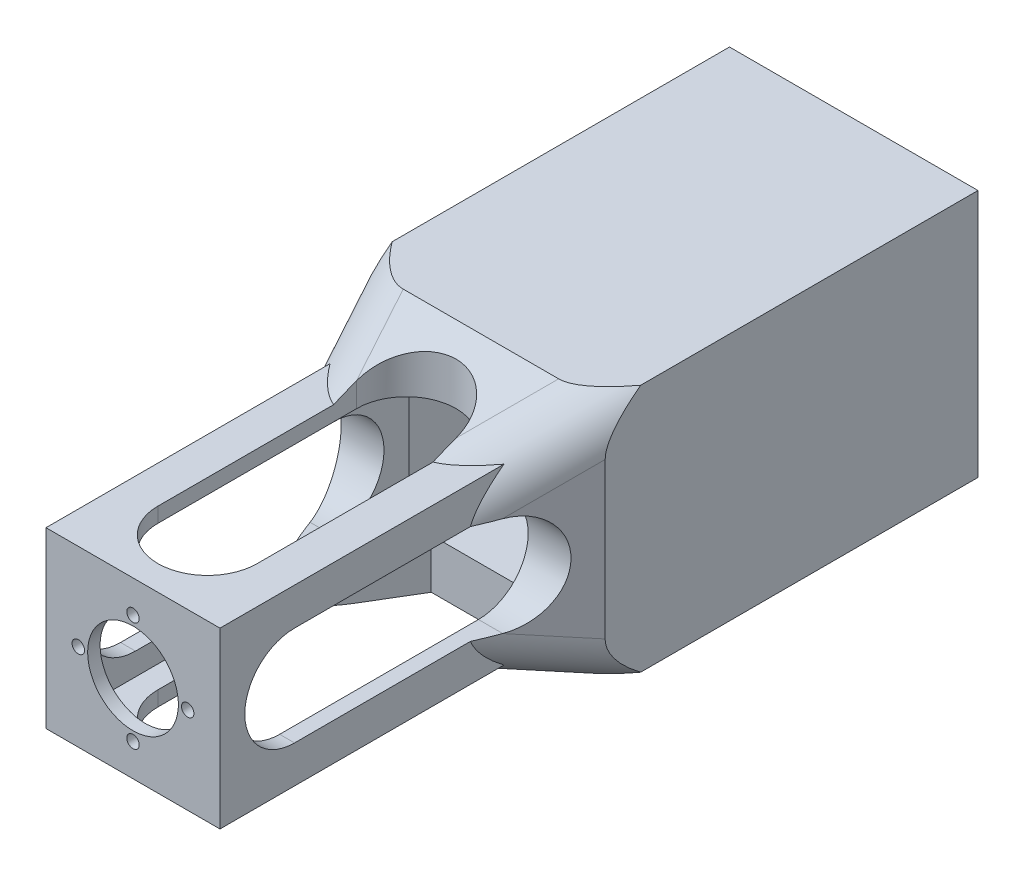
SolidWorks part; units mm, degrees
ref_plane "Ön Düzlem" through (0, 0, 0) normal (0, 0, 1) x (1, 0, 0)
ref_plane "Üst Düzlem" through (0, 0, 0) normal (0, 1, 0) x (1, 0, 0)
ref_plane "Sağ Düzlem" through (0, 0, 0) normal (1, 0, 0) x (0, 0, -1)
sketch "Çizim1" plane through (0, 0, 0) normal (0, 0, 1) x (1, 0, 0)
  line L0 (-14.5, 14.5) -> (14.5, 14.5)
  line L1 (-17.5, 17.5) -> (17.5, 17.5)
  line L2 (-17.5, 17.5) -> (-17.5, -17.5)
  line L3 (-17.5, -17.5) -> (17.5, -17.5)
  line L4 (17.5, 17.5) -> (17.5, -17.5)
  line L5 (-17.5, 17.5) -> (17.5, -17.5) construction
  line L6 (-17.5, -17.5) -> (17.5, 17.5) construction
  line L7 (14.5, 14.5) -> (14.5, -14.5)
  line L8 (-14.5, -14.5) -> (14.5, -14.5)
  line L9 (-14.5, 14.5) -> (-14.5, -14.5)
  point P0 (0, 0)
  dimension "D1" = 35
  dimension "D2" = 3
extrude "Yükseklik-Ekstrüzyon1" add sketch "Çizim1" along normal mid plane 70
sketch "Çizim2" plane through (0, 0, 35) normal (0, 0, 1) x (1, 0, 0)
  line L1 (-17.5, -17.5) -> (17.5, -17.5)
  line L2 (-17.5, -17.5) -> (-17.5, 17.5)
  line L3 (-17.5, 17.5) -> (17.5, 17.5)
  line L4 (17.5, -17.5) -> (17.5, 17.5)
  line L5 (-17.5, -17.5) -> (17.5, 17.5) construction
  line L6 (-17.5, 17.5) -> (17.5, -17.5) construction
  point P0 (0, 0)
extrude "Yükseklik-Ekstrüzyon2" add sketch "Çizim2" against normal blind 2.5
ref_axis "Eksen1" through (0, 0, -55) along (0, 0, 1)
sketch "Çizim7" plane through (0, 0, 35) normal (0, 0, 1) x (1, 0, 0)
  circle A0 centre (-11, 0) radius 1.25
  circle A1 centre (11, 0) radius 1.25
  circle A2 centre (0, 11) radius 1.25
  circle A3 centre (0, -11) radius 1.25
extrude "Kes-Ekstrüzyon5" cut sketch "Çizim7" against normal through all
sketch "Çizim5" plane through (0, 0, 32.5) normal (0, 0, -1) x (-1, 0, 0)
  circle A0 centre (0, 0) radius 9.125
  dimension "D1" = 18.25
extrude "Kes-Ekstrüzyon3" cut sketch "Çizim5" against normal through all contours A0
sketch "Çizim10" plane through (0, 0, -35) normal (0, 0, -1) x (-1, 0, 0)
  line L1 (-25, 25) -> (25, 25)
  line L2 (-25, 25) -> (-25, -25)
  line L3 (-25, -25) -> (25, -25)
  line L4 (25, 25) -> (25, -25)
  line L5 (-25, 25) -> (25, -25) construction
  line L6 (-25, -25) -> (25, 25) construction
  line L7 (-15.05, -15.05) -> (15.05, -15.05)
  line L8 (-15.05, -15.05) -> (-15.05, 15.05)
  line L9 (-15.05, 15.05) -> (15.05, 15.05)
  line L10 (15.05, -15.05) -> (15.05, 15.05)
  line L11 (-15.05, -15.05) -> (15.05, 15.05) construction
  line L12 (-15.05, 15.05) -> (15.05, -15.05) construction
  point P0 (0, 0)
  point P6 (0, 0)
  point P12 (15.9507, 15.9507)
  dimension "D1" = 50
  dimension "D2" = 30.1
extrude "Yükseklik-Ekstrüzyon3" add sketch "Çizim10" along normal blind 75 separate body
sketch "Çizim12" plane through (0, 0, -35) normal (0, 0, 1) x (1, 0, 0)
  line L0 (-17.5, -17.5) -> (17.5, -17.5) construction
  line L1 (17.5, -17.5) -> (17.5, 17.5) construction
  line L2 (17.5, 17.5) -> (-17.5, 17.5) construction
  line L3 (-17.5, 17.5) -> (-17.5, -17.5) construction
  line L4 (-25, 25) -> (-25, -25)
  line L5 (-25, -25) -> (25, -25)
  line L6 (25, -25) -> (25, 25)
  line L7 (25, 25) -> (-25, 25)
  line L8 (-25, 25) -> (-25, -25)
  line L9 (-25, -25) -> (25, -25)
  line L10 (25, -25) -> (25, 25)
  line L11 (25, 25) -> (-25, 25)
  line L12 (-17.5, -17.5) -> (17.5, -17.5)
  line L13 (17.5, -17.5) -> (17.5, 17.5)
  line L14 (17.5, 17.5) -> (-17.5, 17.5)
  line L15 (-17.5, 17.5) -> (-17.5, -17.5)
  dimension "D1" = 0
extrude "Yükseklik-Ekstrüzyon4" add sketch "Çizim12" along normal blind 20
sketch "Çizim3" plane through (0, 17.5, 0) normal (0, 1, 0) x (1, 0, 0)
  line L0 (0, 20) -> (0, -20) construction
  line L1 (10, 20) -> (10, -20)
  line L2 (-10, 20) -> (-10, -20)
  arc A0 (10, 20) -> (-10, 20) centre (0, 20) ccw
  arc A1 (-10, -20) -> (10, -20) centre (0, -20) ccw
  point P3 (0, 0)
  dimension "D1" = 10
  dimension "D2" = 40
extrude "Kes-Ekstrüzyon1" cut sketch "Çizim3" against normal through all
sketch "Çizim8" plane through (0, -17.5, 0) normal (0, -1, 0) x (1, 0, 0)
  line L0 (-10, -20) -> (-10, -35)
  line L1 (-17.5, -35) -> (17.5, -35) construction
  line L2 (-10, -35) -> (10, -35)
  line L3 (10, -35) -> (10, -20)
  arc A0 (-10, -20) -> (10, -20) centre (0, -20) ccw construction
  arc A1 (-10, -20) -> (10, -20) centre (0, -20) ccw
extrude "Kes-Ekstrüzyon6" cut sketch "Çizim8" against normal blind 10
pattern_circular "Dairesel Kaplama1" count 4 over 360 about axis through (0, 0, -55) along (0, 0, 1) of "Kes-Ekstrüzyon1"
sketch "Çizim13" plane through (25, 0, 0) normal (1, 0, 0) x (0, 0, -1)
  line L0 (15, 25) -> (15, 17.5)
  line L1 (15, 10) -> (15, 25) construction
  line L2 (15, 17.5) -> (35, 25)
  line L3 (15, 25) -> (110, 25) construction
  line L4 (35, 25) -> (15, 25)
  line L5 (15, -17.5) -> (15, -25)
  line L6 (15, -25) -> (15, -10) construction
  line L7 (15, -25) -> (35, -25)
  line L8 (15, -25) -> (110, -25) construction
  line L9 (35, -25) -> (15, -17.5)
  dimension "D1" = 20
extrude "Kes-Ekstrüzyon7" cut sketch "Çizim13" against normal through all
sketch "Çizim14" plane through (0, -25, 0) normal (0, -1, 0) x (1, 0, 0)
  line L0 (-17.5, -15) -> (-25, -35)
  line L1 (-25, -35) -> (-25, -15)
  line L2 (-25, -15) -> (-17.5, -15)
  line L3 (17.5, -15) -> (25, -15)
  line L4 (25, -15) -> (25, -35)
  line L5 (25, -35) -> (17.5, -15)
extrude "Kes-Ekstrüzyon8" cut sketch "Çizim14" against normal through all
fillet "Radyus4" radius 10 4 edges at (21.25, 21.25, -25) (-21.25, 21.25, -25) (21.25, -21.25, -25) (-21.25, -21.25, -25)
sketch "Çizim15" plane through (0, -17.5, 0) normal (0, 1, 0) x (1, 0, 0)
  line L6 (10, 20) -> (10, 35)
  line L7 (10, 35) -> (-10, 35)
  line L8 (-10, 35) -> (-10, 20)
  line L11 (10, 20) -> (10, 35)
  line L12 (10, 35) -> (-10, 35)
  line L13 (-10, 35) -> (-10, 20)
  arc A1 (10, 20) -> (-10, 20) centre (0, 20) ccw
  arc A2 (10, 20) -> (-10, 20) centre (0, 20) ccw
  dimension "D1" = 0
extrude "Kes-Ekstrüzyon9" cut sketch "Çizim15" against normal through all
